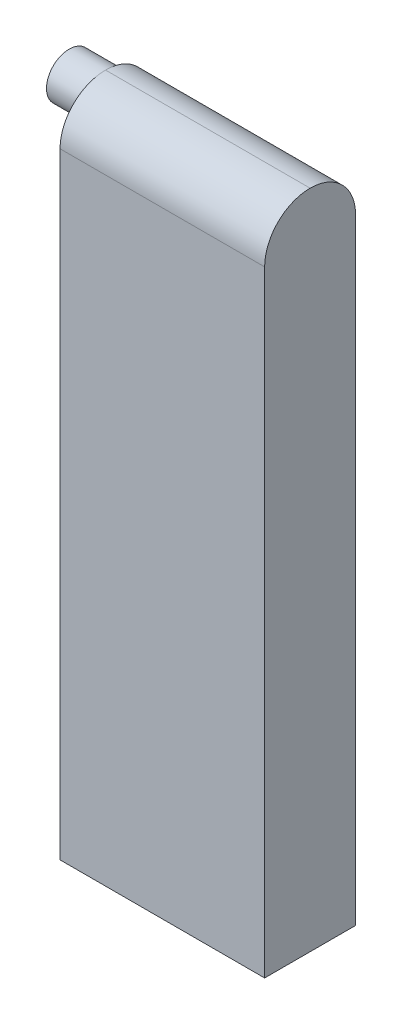
SolidWorks part; units mm, degrees
ref_plane "Alzado" through (0, 0, 0) normal (0, 0, 1) x (1, 0, 0)
ref_plane "Planta" through (0, 0, 0) normal (0, 1, 0) x (1, 0, 0)
ref_plane "Vista lateral" through (0, 0, 0) normal (1, 0, 0) x (0, 0, -1)
sketch "Croquis1" plane through (0, 0, 0) normal (0, 0, 1) x (1, 0, 0)
  line L1 (0, 0) -> (-45, 0)
  line L2 (0, 0) -> (0, 145.5)
  line L3 (0, 145.5) -> (-45, 145.5)
  line L4 (-45, 0) -> (-45, 145.5)
  dimension "D1" = 45
  dimension "D2" = 145.5
extrude "Saliente-Extruir1" add sketch "Croquis1" along normal blind 20
fillet "Redondeo1" radius 10 2 edges at (-22.5, 145.5, 0) (-22.5, 145.5, 20)
sketch "Croquis2" plane through (-45, 0, 0) normal (-1, 0, 0) x (0, 0, 1)
  circle A0 centre (10, 140.5) radius 5
  dimension "D1" = 10
extrude "Saliente-Extruir2" add sketch "Croquis2" along normal blind 8
